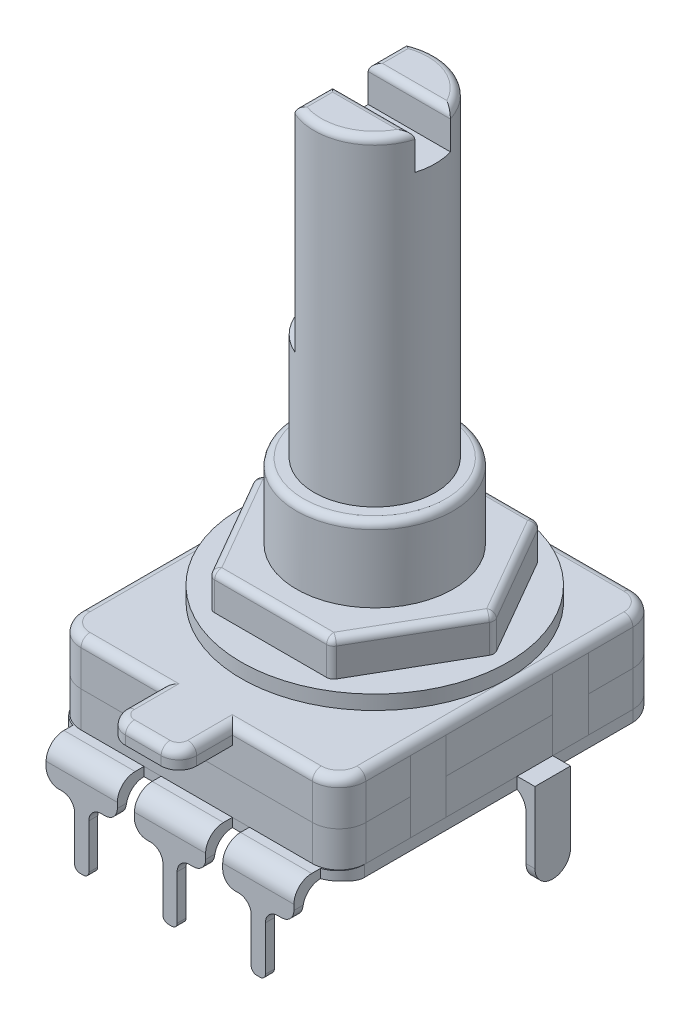
SolidWorks part; units mm, degrees
ref_plane "Alzado" through (0, 0, 0) normal (0, 0, 1) x (1, 0, 0)
ref_plane "Planta" through (0, 0, 0) normal (0, 1, 0) x (1, 0, 0)
ref_plane "Vista lateral" through (0, 0, 0) normal (1, 0, 0) x (0, 0, -1)
sketch "Croquis1" plane through (0, 0, 0) normal (0, 1, 0) x (1, 0, 0)
  line L0 (6, -1) -> (10, -1)
  line L1 (10, 0) -> (10.96, 0)
  line L2 (0, 12) -> (0, 18)
  line L3 (0, 18) -> (16, 18)
  line L5 (10.96, -1) -> (14.96, -1)
  line L6 (6, 0) -> (6, -1)
  line L7 (0, 0) -> (0, 10)
  line L8 (14.96, 0) -> (14.96, -1)
  line L9 (10, 0) -> (10, -1)
  line L10 (10.96, 0) -> (10.96, -1)
  line L11 (1.04, -1) -> (5.04, -1)
  line L12 (0, 10) -> (-1, 10)
  line L13 (5.04, 0) -> (5.04, -1)
  line L14 (1.04, 0) -> (1.04, -1)
  line L15 (0, 0) -> (1.04, 0)
  line L16 (5.04, 0) -> (6, 0)
  line L17 (-1, 10) -> (-1, 12)
  line L18 (14.96, 0) -> (16, 0)
  line L19 (-1, 12) -> (0, 12)
  line L20 (10, 0) -> (10, -1) [skipped]
  line L21 (10, 0) -> (10, -1) [skipped]
  line L22 (6, -1) -> (6, 0) [skipped]
  line L23 (6, -1) -> (6, 0) [skipped]
  line L24 (10.96, -1) -> (10.96, 0) [skipped]
  line L25 (14.96, 0) -> (14.96, -1) [skipped]
  line L26 (1.04, -1) -> (1.04, 0) [skipped]
  line L27 (14.96, -1) -> (14.9346, -1.0133) [skipped]
  line L28 (10, -1) -> (9.9746, -1.0133) [skipped]
  line L29 (10, -1) -> (9.9746, -1.0133) [skipped]
  line L30 (5.04, -1) -> (5.0146, -1.0133) [skipped]
  line L31 (17, 12) -> (16, 12)
  line L32 (17, 10) -> (17, 12)
  line L33 (16, 10) -> (17, 10)
  line L34 (16, 0) -> (16, 10)
  line L35 (16, 12) -> (16, 18)
  dimension "D1" = 18
  dimension "D2" = 16
extrude "Extruir2" add sketch "Croquis1" along normal blind 0.5
sketch "Croquis2" plane through (0, 0.5, 0) normal (0, 1, 0) x (1, 0, 0)
  line L1 (0, 18) -> (16, 18)
  line L2 (0, 18) -> (0, 0)
  line L3 (0, 0) -> (16, 0)
  line L4 (16, 18) -> (16, 0)
extrude "Extruir4" add sketch "Croquis2" along normal blind 2 separate body
sketch "Croquis4" plane through (0, 2.5, 0) normal (0, 1, 0) x (1, 0, 0)
  line L1 (0, 18) -> (16, 18)
  line L2 (0, 18) -> (0, 0)
  line L3 (0, 0) -> (16, 0)
  line L4 (16, 18) -> (16, 0)
extrude "Extruir5" add sketch "Croquis4" along normal blind 2.5 separate body
sketch "Croquis5" plane through (0, 5, 0) normal (0, 1, 0) x (1, 0, 0)
  line L1 (6, 0) -> (10, 0)
  line L2 (6, 0) -> (6, -2)
  line L3 (7, -3) -> (9, -3)
  line L4 (10, 0) -> (10, -2)
  arc A0 (7, -3) -> (6, -2) centre (7, -2) cw
  arc A1 (9, -3) -> (10, -2) centre (9, -2) ccw
  point P6 (6, -3)
  point P9 (10, -3)
  dimension "D3" = 1
  dimension "D1" = 3
  dimension "D2" = 4
extrude "Extruir6" add sketch "Croquis5" against normal blind 1
sketch "Croquis6" plane through (0, 5, 0) normal (0, 1, 0) x (1, 0, 0)
  line L0 (0, 14) -> (0, 12)
  line L1 (0, 18) -> (0, 0) construction
  line L2 (0, 14) -> (3, 14)
  line L3 (3, 14) -> (3, 12)
  line L4 (3, 12) -> (0, 12)
  line L8 (13, 12) -> (16, 12)
  line L9 (13, 14) -> (13, 12)
  line L10 (16, 14) -> (13, 14)
  line L11 (16, 14) -> (16, 12)
  line L12 (16, 4) -> (16, 6)
  line L13 (16, 4) -> (13, 4)
  line L14 (13, 4) -> (13, 6)
  line L15 (13, 6) -> (16, 6)
  line L16 (3, 6) -> (0, 6)
  line L17 (3, 4) -> (3, 6)
  line L18 (0, 4) -> (3, 4)
  line L19 (0, 4) -> (0, 6)
sketch "Croquis7" plane through (0, 5, 0) normal (0, 1, 0) x (1, 0, 0)
  line L0 (3, 12) -> (0, 12) construction
  line L1 (0, 14) -> (0.5, 14)
  line L2 (0, 14) -> (0, 12)
  line L3 (0, 12) -> (0.5, 12)
  line L4 (0.5, 14) -> (0.5, 12)
  line L7 (16, 4) -> (15.5, 4)
  line L9 (0.5, 4) -> (0.5, 6)
  line L10 (0, 6) -> (0.5, 6)
  line L11 (0, 4) -> (0, 6)
  line L12 (0, 4) -> (0.5, 4)
  line L13 (16, 4) -> (16, 6)
  line L14 (16, 6) -> (15.5, 6)
  line L15 (15.5, 4) -> (15.5, 6)
  line L16 (15.5, 14) -> (15.5, 12)
  line L17 (16, 12) -> (15.5, 12)
  line L18 (16, 14) -> (16, 12)
  line L19 (16, 14) -> (15.5, 14)
extrude "Extruir7" cut sketch "Croquis7" against normal blind 4.5
extrude "Extruir8" cut sketch "Croquis6" against normal blind 0.5
sketch "Croquis8" plane through (0, 0.5, 0) normal (0, 1, 0) x (1, 0, 0)
  line L0 (0, 12) -> (3, 12) construction
  line L1 (0, 14) -> (0.5, 14)
  line L2 (0, 14) -> (0, 12)
  line L3 (0, 12) -> (0.5, 12)
  line L4 (0.5, 14) -> (0.5, 12)
  line L5 (0.5, 12) -> (3, 12) construction
  line L6 (16, 6) -> (13, 6) construction
  line L7 (15.5, 14) -> (16, 14)
  line L8 (15.5, 14) -> (15.5, 12)
  line L9 (15.5, 12) -> (16, 12)
  line L10 (16, 14) -> (16, 12)
  line L11 (15.5, 6) -> (16, 6)
  line L12 (15.5, 6) -> (15.5, 4)
  line L13 (15.5, 4) -> (16, 4)
  line L14 (16, 6) -> (16, 4)
  line L16 (0, 6) -> (0.5, 6)
  line L17 (0, 6) -> (0, 4)
  line L18 (0, 4) -> (0.5, 4)
  line L19 (0.5, 6) -> (0.5, 4)
extrude "Extruir14" add sketch "Croquis8" along normal blind 4 separate body
sketch "Croquis9" plane through (0, 4.5, 0) normal (0, 1, 0) x (-1, 0, 0)
  line L1 (0, -14) -> (-3, -14)
  line L2 (0, -14) -> (0, -12)
  line L3 (0, -12) -> (-3, -12)
  line L4 (-3, -14) -> (-3, -12)
  line L5 (-13, -14) -> (-16, -14)
  line L6 (-13, -14) -> (-13, -12)
  line L7 (-13, -12) -> (-16, -12)
  line L8 (-16, -14) -> (-16, -12)
  line L9 (-16, -4) -> (-13, -4)
  line L10 (-16, -4) -> (-16, -6)
  line L11 (-16, -6) -> (-13, -6)
  line L12 (-13, -4) -> (-13, -6)
  line L13 (0, -4) -> (-3, -4)
  line L14 (0, -4) -> (0, -6)
  line L15 (0, -6) -> (-3, -6)
  line L16 (-3, -4) -> (-3, -6)
extrude "Extruir16" add sketch "Croquis9" along normal blind 0.5 separate body
sketch "Croquis10" plane through (0, 0, 1) normal (0, 0, 1) x (1, 0, 0)
  line L0 (9.1, -1.5) -> (9.3, -1.5)
  line L1 (6, 0.5) -> (10, 0.5)
  line L2 (6, 0.5) -> (6, -0.8)
  line L3 (6.7, -1.5) -> (6.9, -1.5)
  line L4 (10, 0.5) -> (10, -0.8)
  line L5 (14.06, -1.5) -> (14.26, -1.5)
  line L6 (10.96, 0.5) -> (14.96, 0.5)
  line L7 (10.96, 0.5) -> (10.96, -0.8)
  line L8 (7.6, -2.2) -> (7.6, -4.7)
  line L9 (7.9, -5) -> (8.1, -5)
  line L10 (8.4, -2.2) -> (8.4, -4.7)
  line L11 (11.66, -1.5) -> (11.86, -1.5)
  line L12 (14.96, 0.5) -> (14.96, -0.8)
  line L13 (12.56, -2.2) -> (12.56, -4.7)
  line L14 (12.86, -5) -> (13.06, -5)
  line L15 (13.36, -2.2) -> (13.36, -4.7)
  line L16 (4.14, -1.5) -> (4.34, -1.5)
  line L17 (1.04, 0.5) -> (5.04, 0.5)
  line L18 (1.04, 0.5) -> (1.04, -0.8)
  line L19 (1.74, -1.5) -> (1.94, -1.5)
  line L20 (5.04, 0.5) -> (5.04, -0.8)
  line L21 (2.64, -2.2) -> (2.64, -4.7)
  line L22 (2.94, -5) -> (3.14, -5)
  line L23 (3.44, -2.2) -> (3.44, -4.7)
  arc A0 (6, -0.8) -> (6.7, -1.5) centre (6.7, -0.8) ccw
  arc A1 (10, -0.8) -> (9.3, -1.5) centre (9.3, -0.8) cw
  arc A2 (9.1, -1.5) -> (8.4, -2.2) centre (9.1, -2.2) ccw
  arc A3 (6.9, -1.5) -> (7.6, -2.2) centre (6.9, -2.2) cw
  arc A4 (7.9, -5) -> (7.6, -4.7) centre (7.9, -4.7) cw
  arc A5 (8.4, -4.7) -> (8.1, -5) centre (8.1, -4.7) cw
  arc A6 (10.96, -0.8) -> (11.66, -1.5) centre (11.66, -0.8) ccw
  arc A7 (14.96, -0.8) -> (14.26, -1.5) centre (14.26, -0.8) cw
  arc A8 (14.06, -1.5) -> (13.36, -2.2) centre (14.06, -2.2) ccw
  arc A9 (11.86, -1.5) -> (12.56, -2.2) centre (11.86, -2.2) cw
  arc A10 (12.86, -5) -> (12.56, -4.7) centre (12.86, -4.7) cw
  arc A11 (13.36, -4.7) -> (13.06, -5) centre (13.06, -4.7) cw
  arc A12 (1.04, -0.8) -> (1.74, -1.5) centre (1.74, -0.8) ccw
  arc A13 (5.04, -0.8) -> (4.34, -1.5) centre (4.34, -0.8) cw
  arc A14 (4.14, -1.5) -> (3.44, -2.2) centre (4.14, -2.2) ccw
  arc A15 (1.94, -1.5) -> (2.64, -2.2) centre (1.94, -2.2) cw
  arc A16 (2.94, -5) -> (2.64, -4.7) centre (2.94, -4.7) cw
  arc A17 (3.44, -4.7) -> (3.14, -5) centre (3.14, -4.7) cw
  point P11 (6, -1.5)
  point P14 (10, -1.5)
  point P17 (8.4, -1.5)
  point P24 (8.4, -5)
  dimension "D4" = 0.7
  dimension "D5" = 0.3
  dimension "D1" = 4
  dimension "D2" = 2
  dimension "D3" = 3.5
extrude "Extruir17" add sketch "Croquis10" along normal blind 0.5
sketch "Croquis11" plane through (0, 5, 0) normal (0, 1, 0) x (1, 0, 0)
  circle A0 centre (8, 10) radius 4.4
extrude "Extruir20" add sketch "Croquis11" along normal blind 7
sketch "Croquis12" plane through (0, 12, 0) normal (0, 1, 0) x (1, 0, 0)
  circle A0 centre (8, 10) radius 3.4
extrude "Extruir21" add sketch "Croquis12" along normal blind 18
sketch "Croquis13" plane through (0, 30, 0) normal (0, 1, 0) x (1, 0, 0)
  line L0 (6.6345, 13.1137) -> (6.6345, 6.8863)
  arc A2 (6.6345, 13.1137) -> (6.6345, 6.8863) centre (8, 10) ccw
extrude "Extruir22" cut sketch "Croquis13" against normal blind 12
sketch "Croquis14" plane through (0, 30, 0) normal (0, 1, 0) x (1, 0, 0)
  line L0 (6.6345, 11) -> (6.6345, 9)
  line L2 (6.6345, 9) -> (11.2496, 9)
  line L3 (6.6345, 11) -> (11.2496, 11)
  line L5 (6.6345, 13.1137) -> (6.6345, 6.8863)
  arc A2 (6.6345, 6.8863) -> (6.6345, 13.1137) centre (8, 10) ccw
  arc A3 (11.2496, 9) -> (11.2496, 11) centre (8, 10) ccw
  dimension "D1" = 0
extrude "Extruir23" cut sketch "Croquis14" against normal blind 2
sketch "Croquis16" plane through (0, 5, 0) normal (0, 1, 0) x (1, 0, 0)
  circle A1 centre (8, 10) radius 4.4
  circle A2 centre (8, 10) radius 7.5
  circle A3 centre (8, 10) radius 7.5
  dimension "D1" = 3.1
  dimension "D3" = 3.1
extrude "Extruir24" add sketch "Croquis16" along normal blind 0.8
sketch "Croquis17" plane through (0, 5.8, 0) normal (0, 1, 0) x (1, 0, 0)
  line L6 (1.25, 10) -> (4.625, 15.8457)
  line L7 (11.375, 15.8457) -> (14.75, 10)
  line L8 (4.625, 15.8457) -> (11.375, 15.8457)
  line L9 (11.375, 4.1543) -> (14.75, 10)
  line L10 (4.625, 4.1543) -> (11.375, 4.1543)
  line L11 (4.625, 4.1543) -> (1.25, 10)
  circle A3 centre (8, 10) radius 4.4
  circle A4 centre (8, 10) radius 4.4
  dimension "D1" = 0
extrude "Extruir25" add sketch "Croquis17" along normal blind 2
sketch "Croquis18" plane through (0, 0, 0) normal (0, -1, 0) x (1, 0, 0)
  line L0 (0, -12) -> (-1, -12) construction
  line L1 (-1, -10) -> (-0.5, -10)
  line L2 (-1, -10) -> (-1, -12)
  line L3 (-1, -12) -> (-0.5, -12)
  line L4 (-0.5, -10) -> (-0.5, -12)
  line L5 (17, -12) -> (16, -12) construction
  line L6 (17, -10) -> (16.5, -10)
  line L7 (17, -10) -> (17, -12)
  line L8 (17, -12) -> (16.5, -12)
  line L9 (16.5, -10) -> (16.5, -12)
extrude "Extruir26" add sketch "Croquis18" along normal blind 4.5
fillet "Redondeo1" radius 1 3 edges at (12.96, 0.5, 1.5) (8, 0.5, 1.5) (3.04, 0.5, 1.5)
fillet "Redondeo2" radius 1 1 edges at (-1, 0.5, -11)
fillet "Redondeo3" radius 1 1 edges at (-0.5, 0, -11)
fillet "Redondeo4" radius 1 1 edges at (16.5, 0, -11)
fillet "Redondeo5" radius 1 3 edges at (12.96, 0, 1) (3.04, 0, 1) (8, 0, 1)
fillet "Redondeo6" radius 1 2 edges at (-0.75, -4.5, -12) (-0.75, -4.5, -10)
fillet "Redondeo7" radius 1 2 edges at (16.75, -4.5, -12) (16.75, -4.5, -10)
fillet "Redondeo8" radius 1.5 1 edges at (16, 3.75, 0)
fillet "Redondeo9" radius 1.5 1 edges at (16, 1.5, 0)
fillet "Redondeo10" radius 1.5 1 edges at (16, 0.183, 0)
fillet "Redondeo11" radius 1.5 1 edges at (0, 1.5, 0)
fillet "Redondeo12" radius 1.5 1 edges at (0, 3.75, 0)
fillet "Redondeo13" radius 1.5 1 edges at (0, 0.183, 0)
fillet "Redondeo14" radius 1.5 1 edges at (0, 3.75, -18)
fillet "Redondeo15" radius 1.5 1 edges at (0, 1.5, -18)
fillet "Redondeo16" radius 1.5 1 edges at (0, 0.183, -18)
fillet "Redondeo17" radius 1.5 1 edges at (16, 3.75, -18)
fillet "Redondeo18" radius 1.5 1 edges at (16, 1.5, -18)
fillet "Redondeo19" radius 1.5 1 edges at (16, 0.183, -18)
fillet "Redondeo20" radius 0.4 12 edges at (11.375, 6.8, -15.8457) (14.75, 6.8, -10) (4.625, 6.8, -15.8457) (1.25, 6.8, -10) (4.625, 6.8, -4.1543) (11.375, 6.8, -4.1543) (8, 7.8, -15.8457) (2.9375, 7.8, -12.9228) (2.9375, 7.8, -7.0772) (8, 7.8, -4.1543) (13.0625, 7.8, -7.0772) (13.0625, 7.8, -12.9228)
fillet "Redondeo21" radius 0.4 1 edges at (8, 12, -5.6)
fillet "Redondeo22" radius 0.4 3 edges at (9.4158, 30, -6.9088) (6.6345, 30, -7.9431) (8.942, 30, -9)
fillet "Redondeo23" radius 0.4 3 edges at (6.6345, 30, -12.0569) (9.4158, 30, -13.0912) (8.942, 30, -11)
fillet "Redondeo24" radius 0.5 14 edges at (6.2929, 5, 2.7071) (8, 5, 3) (9.7071, 5, 2.7071) (15.5607, 5, -0.4393) (0.4393, 5, -0.4393) (0, 5, -9) (0.4393, 5, -17.5607) (8, 5, -18) (15.5607, 5, -17.5607) (16, 5, -9)
